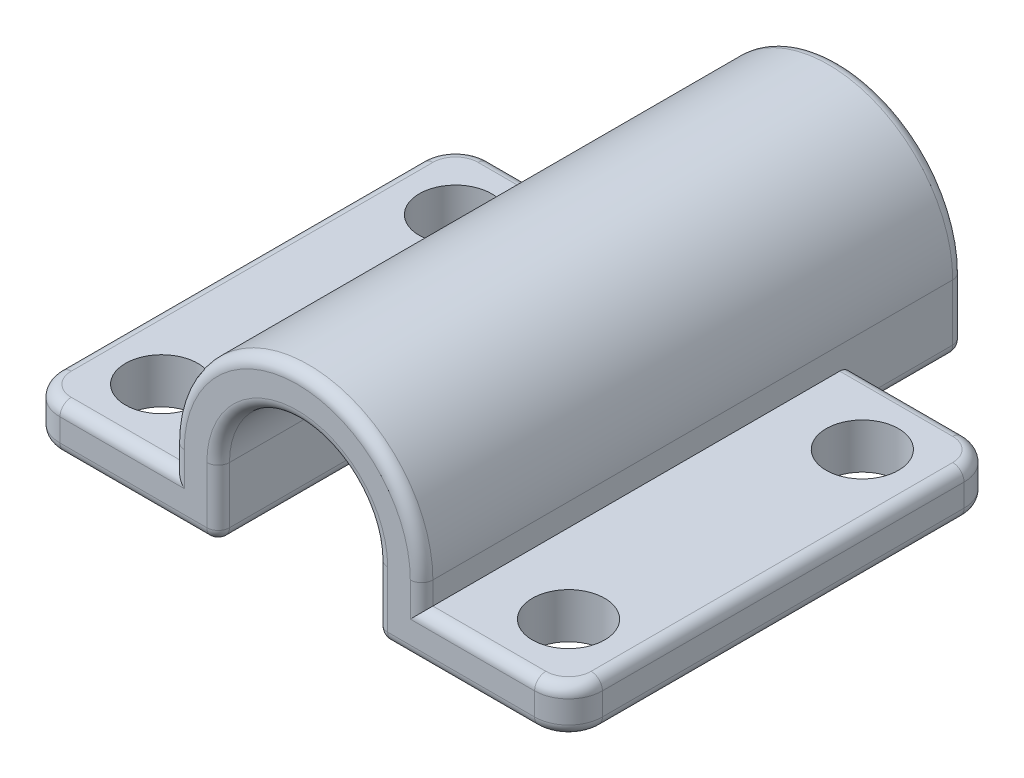
SolidWorks part; units mm, degrees
ref_plane "Front Plane" through (0, 0, 0) normal (0, 0, 1) x (1, 0, 0)
ref_plane "Top Plane" through (0, 0, 0) normal (0, 1, 0) x (1, 0, 0)
ref_plane "Right Plane" through (0, 0, 0) normal (1, 0, 0) x (0, 0, -1)
sketch "Sketch1" plane through (0, 0, 0) normal (0, 0, 1) x (1, 0, 0)
  line L0 (0, -1) -> (0, -3) construction
  line L1 (-12, -1) -> (12, -1)
  line L2 (-12, -1) -> (-12, -3)
  line L3 (-12, -3) -> (12, -3)
  line L4 (12, -1) -> (12, -3)
  line L5 (-11.2192, -3.5) -> (11.2192, -3.5) construction
  line L6 (-3.5, 0) -> (-3.5, -1)
  line L7 (3.5, 0) -> (3.5, -1)
  line L8 (5.5, 0) -> (5.5, -1)
  line L9 (-5.5, 0) -> (-5.5, -1)
  line L10 (-3.5, -1) -> (-3.5, -3)
  line L11 (3.5, -1) -> (3.5, -3)
  circle A0 centre (0, 0) radius 3.5
  circle A1 centre (0, 0) radius 5.5
  point P14 (0, -3.5)
  dimension "D1" = 7
  dimension "D2" = 2
  dimension "D3" = 2
  dimension "D4" = 1
  dimension "D5" = 24
extrude "Boss-Extrude1" add sketch "Sketch1" along normal blind 19 contours A1 L1 L6 A0 L7 | A1 L1 L8 | A1 L9 L1 | A1 L1 L2 L3 | L1 A1 L3 L10 | L3 A1 L1 L11 | A1 L3 L4 L1 region at (-8.5389, -2.0191, 0) region at (-5.4725, -0.7504, 0) region at (-5.3498, -0.4904, 0) region at (-4.3096, -1.9168, 0) region at (5.4725, -0.7504, 0) region at (8.5389, -2.0191, 0) region at (4.3096, -1.9168, 0)
sketch "Sketch2" plane through (0, -1, 0) normal (0, 1, 0) x (1, 0, 0)
  line L0 (-9, -3) -> (9, -3) construction
  line L1 (-12, 0) -> (12, 0)
  line L2 (0, 0) -> (0, -19) construction
  line L3 (-5.5, -19) -> (5.5, -19) construction
  point P1 (9, -3)
  point P11 (-9, -3)
  point P12 (0, -3)
  dimension "D1" = 18
  dimension "D2" = 3
hole_wizard "M3 Clearance Hole1" positions "Sketch2" profile "Sketch4" hole size "M3" standard "ANSI Metric" end condition through all
sketch "Sketch4" plane through (9, -1, 3) normal (1, 0, 0) x (0, 0, 1)
  line L0 (0, 0) -> (0, 2)
  line L1 (0, 2) -> (1.6, 2)
  line L2 (1.6, 2) -> (1.6, 0)
  line L5 (1.6, 0) -> (0, 0)
  line L11 (0, -6.35) -> (0, 107.95) construction
  dimension "Thru Hole Dia." = 3.2
  dimension "Thru Hole Depth" = 2
sketch "Sketch5" plane through (0, 0, 0) normal (0, 0, -1) x (-1, 0, 0)
  line L0 (-5.5, -1) -> (-5.5, -3)
  line L1 (5.5, -1) -> (5.5, -3)
  line L10 (-5.5, -1) -> (-12, -1)
  line L11 (-12, -1) -> (-12, -3)
  line L12 (-12, -3) -> (-3.5, -3)
  line L13 (-3.5, -3) -> (-3.5, 0)
  line L14 (3.5, 0) -> (3.5, -3)
  line L15 (3.5, -3) -> (12, -3)
  line L16 (12, -3) -> (12, -1)
  line L17 (12, -1) -> (5.5, -1)
  line L18 (5.5, -1) -> (5.5, 0)
  line L19 (-5.5, 0) -> (-5.5, -1)
  line L20 (-5.5, -1) -> (-12, -1)
  line L21 (-12, -1) -> (-12, -3)
  line L22 (-12, -3) -> (-3.5, -3)
  line L23 (-3.5, -3) -> (-3.5, 0)
  line L24 (3.5, 0) -> (3.5, -3)
  line L25 (3.5, -3) -> (12, -3)
  line L26 (12, -3) -> (12, -1)
  line L27 (12, -1) -> (5.5, -1)
  line L28 (5.5, -1) -> (5.5, 0)
  line L29 (-5.5, 0) -> (-5.5, -1)
  arc A2 (3.5, 0) -> (-3.5, 0) centre (0, 0) ccw
  arc A3 (5.5, 0) -> (-5.5, 0) centre (0, 0) ccw
  arc A4 (3.5, 0) -> (-3.5, 0) centre (0, 0) ccw
  arc A5 (5.5, 0) -> (-5.5, 0) centre (0, 0) ccw
  line M15 (-12, -3) -> (-3.5, -3)
  line M16 (-3.5, -3) -> (-3.5, 0)
  arc M17 (-3.5, 0) -> (3.5, 0) centre (0, 0) cw
  line M18 (3.5, 0) -> (3.5, -3)
  line M19 (3.5, -3) -> (12, -3)
  line M22 (5.5, -1) -> (5.5, 0)
  arc M23 (5.5, 0) -> (-5.5, 0) centre (0, 0) ccw
  line M24 (-5.5, 0) -> (-5.5, -1)
  dimension "D1" = 0
extrude "Boss-Extrude2" add sketch "Sketch5" along normal blind 5 contours L1 L0 M22 M23 M24 M15 M16 M17 M18 M19 region at (5.361, -0.5, 0)
sketch "Sketch7" plane through (0, -1, 0) normal (0, 1, 0) x (1, 0, 0)
  line L0 (-12, -19) -> (-5.5, -19) construction
  line L1 (-9, -3) -> (9, -3) construction
  line L2 (-9, -3) -> (-9, -16) construction
  line L3 (-9, -16) -> (9, -16) construction
  line L4 (9, -3) -> (9, -16) construction
  point P1 (9, -16)
  point P2 (-9, -16)
  dimension "D1" = 18
  dimension "D2" = 3
hole_wizard "M3 Clearance Hole2" positions "Sketch7" profile "Sketch8" hole size "M3" standard "ANSI Metric" end condition through all
sketch "Sketch8" plane through (-9, -1, 16) normal (1, 0, 0) x (0, 0, 1)
  line L0 (0, 0) -> (0, 2)
  line L1 (0, 2) -> (1.6, 2)
  line L2 (1.6, 2) -> (1.6, 0)
  line L5 (1.6, 0) -> (0, 0)
  line L11 (0, -6.35) -> (0, 107.95) construction
  dimension "Thru Hole Dia." = 3.2
  dimension "Thru Hole Depth" = 2
fillet "Fillet1" radius 1.5 4 edges at (12, -2, 19) (12, -2, 0) (-12, -2, 0) (-12, -2, 19)
fillet "Fillet2" radius 0.5 38 edges at (-8, -1, 19) (-11.5607, -1, 18.5607) (-12, -1, 9.5) (-11.5607, -1, 0.4393) (8, -1, 19) (11.5607, -1, 18.5607) (12, -1, 9.5) (11.5607, -1, 0.4393) (-8, -3, 0) (-11.5607, -3, 0.4393) (-12, -3, 9.5) (-11.5607, -3, 18.5607) (8, -3, 0) (11.5607, -3, 0.4393) (12, -3, 9.5) (11.5607, -3, 18.5607) (-3.5, -1.5, 19) (0, 3.5, 19) (-3.5, -1.5, -5) (0, 3.5, -5) (5.5, -0.5, 19) (-5.5, -0.5, 19) (-5.5, -1.5, -5) (5.5, -1.5, -5) (-8, -1, 0) (8, -1, 0) (-4.5, -3, -5) (4.5, -3, -5) (3.5, -3, 7) (-3.5, -3, 7) (5.5, -3, -2.5) (-5.5, -3, -2.5) (-7, -3, 19) (7, -3, 19) (3.5, -1.5, 19) (3.5, -1.5, -5) (0, 5.5, 19) (0, 5.5, -5)
